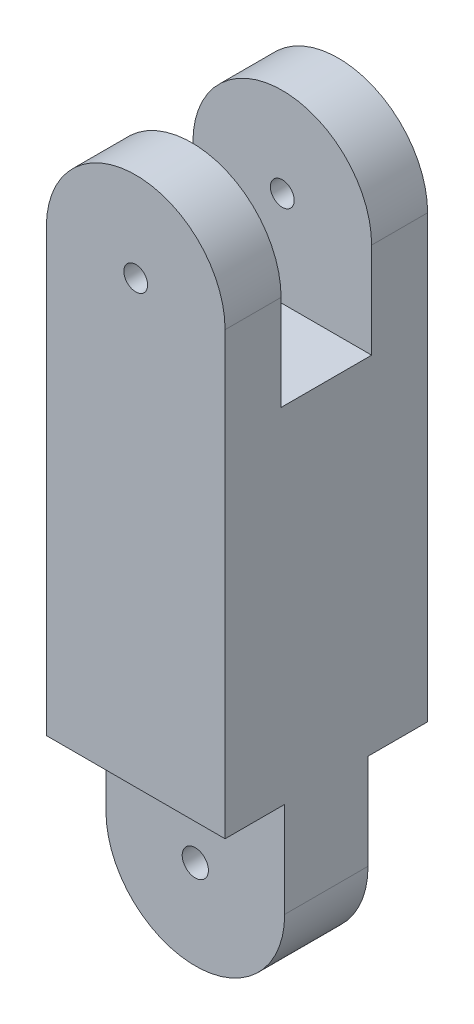
SolidWorks part; units mm, degrees
ref_plane "Front Plane" through (0, 0, 0) normal (0, 0, 1) x (1, 0, 0)
ref_plane "Top Plane" through (0, 0, 0) normal (0, 1, 0) x (1, 0, 0)
ref_plane "Right Plane" through (0, 0, 0) normal (1, 0, 0) x (0, 0, -1)
sketch "Finger_Skeleton" plane through (0, 0, 0) normal (0, 0, -1) x (-1, 0, 0)
  line L0 (0, 0) -> (0, 45)
  line L1 (0, 45) -> (0, 70)
  line L2 (0, 70) -> (0, 93)
  circle A1 centre (0, 0) radius 5 construction
  circle A2 centre (0, 45) radius 5 construction
  circle A3 centre (0, 70) radius 5 construction
  dimension "D4" = 10
  dimension "D5" = 10
  dimension "D6" = 10
  dimension "D1" = 45
  dimension "D2" = 25
  dimension "D3" = 23
sketch "Link1_Outline" plane through (0, 0, 0) normal (0, 0, 1) x (1, 0, 0)
  line L0 (0, 0) -> (0, 45) construction
  line L1 (-7.5, 0) -> (-7.5, 45)
  line L2 (7.5, 0) -> (7.5, 45)
  arc A0 (-7.5, 0) -> (7.5, 0) centre (0, 0) ccw
  arc A1 (7.5, 45) -> (-7.5, 45) centre (0, 45) ccw
  point P4 (0, 22.5)
  dimension "D1" = 15
extrude "Link1_Body" add sketch "Link1_Outline" along normal mid plane 17
sketch "Sketch1" plane through (7.5, 0, 0) normal (1, 0, 0) x (0, 0, -1)
  line L0 (0, 0) -> (0, 45) construction
  line L1 (3.5, -8) -> (9, -8)
  line L2 (3.5, -8) -> (3.5, 7.9981)
  line L3 (3.5, 7.9981) -> (9, 7.9981)
  line L4 (9, -8) -> (9, 7.9981)
  line L5 (-8.5, -7.5) -> (8.5, -7.5) construction
  line L6 (0, 8.25) -> (0, -8.25) construction
  line L7 (-9, -8) -> (-9, 7.9981)
  line L8 (-3.5, 7.9981) -> (-9, 7.9981)
  line L9 (-3.5, -8) -> (-3.5, 7.9981)
  line L10 (-3.5, -8) -> (-9, -8)
  dimension "D1" = 3.5
  dimension "D2" = 5.5
  dimension "D3" = 15.9981
  dimension "D4" = 0.5
extrude "Cut-Extrude1" cut sketch "Sketch1" against normal through all both and the other way through all
sketch "Sketch2" plane through (0, 0, 0) normal (1, 0, 0) x (0, 0, -1)
  line L0 (0, 0) -> (0, 45) construction
  line L1 (3.8, 37) -> (-3.8, 37)
  line L2 (3.8, 37) -> (3.8, 55)
  line L3 (3.8, 55) -> (-3.8, 55)
  line L4 (-3.8, 37) -> (-3.8, 55)
  dimension "D1" = 3.8
  dimension "D2" = 18
  dimension "D3" = 7.6
  dimension "D4" = 37
extrude "Cut-Extrude2" cut sketch "Sketch2" against normal through all both and the other way through all
sketch "Sketch3" plane through (0, 0, 0) normal (0, 0, 1) x (1, 0, 0)
  circle A0 centre (0, 0) radius 1.1
  circle A1 centre (0, 45) radius 1
  dimension "D1" = 2.2
  dimension "D2" = 2
extrude "Cut-Extrude3" cut sketch "Sketch3" against normal through all both and the other way through all
